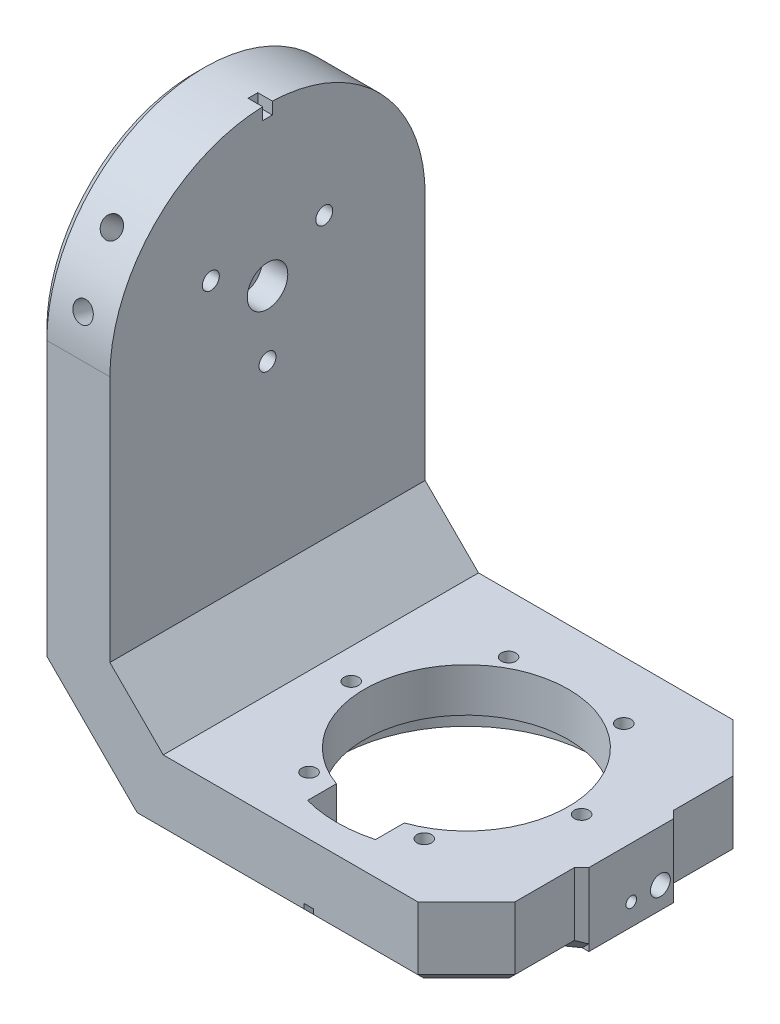
SolidWorks part; units mm, degrees
material "PETG"
ref_plane "Спереди" through (0, 0, 0) normal (0, 0, 1) x (1, 0, 0)
ref_plane "Сверху" through (0, 0, 0) normal (0, 1, 0) x (1, 0, 0)
ref_plane "Справа" through (0, 0, 0) normal (1, 0, 0) x (0, 0, -1)
sketch "Эскиз1" plane through (0, 0, 0) normal (0, 0, 1) x (1, 0, 0)
  line L0 (0, 40) -> (0, -51)
  line L1 (0, -51) -> (11, -62)
  line L2 (11, -62) -> (73.5, -62)
  line L3 (73.5, -62) -> (73.5, -77)
  line L4 (73.5, -77) -> (4.7868, -77)
  line L5 (4.7868, -77) -> (-15, -57.2132)
  line L6 (-15, -57.2132) -> (-15, 40)
  line L7 (-15, 40) -> (0, 40)
  line L8 (41, -24.4112) -> (41, -69.1198) construction
  line L9 (0, 0) -> (71, 0) construction
  dimension "D1" = 15
  dimension "D2" = 40
  dimension "D3" = 45
  dimension "D4" = 15
  dimension "D5" = 15
  dimension "D6" = 41
  dimension "D7" = 32.5
  dimension "D9" = 51
  dimension "D10" = 11
  dimension "D8" = 30
extrude "Бобышка-Вытянуть1" add sketch "Эскиз1" along normal mid plane 65
sketch "Эскиз2" plane through (-15, 0, 0) normal (-1, 0, 0) x (0, 0, 1)
  line L0 (32.5, 40) -> (32.5, -57.2132) construction
  line L1 (32.5, 40) -> (-32.5, 40) construction
  line L2 (-32.5, 40) -> (-32.5, -57.2132) construction
  line L3 (32.5, 40) -> (32.5, 0)
  line L4 (32.5, 40) -> (-32.5, 40)
  line L5 (-32.5, 40) -> (-32.5, -57.2132)
  arc A0 (32.5, 0) -> (-32.5, 0) centre (0, 0) ccw
  circle A1 centre (0, 0) radius 13.5 construction
  circle A2 centre (0, -13.5) radius 1.75
  circle A3 centre (-11.6913, 6.75) radius 1.75
  circle A4 centre (11.6913, 6.75) radius 1.75
  point P17 (0, 0)
  line M3 (-32.5, 40) -> (-32.5, -57.2132)
  line M5 (32.5, -57.2132) -> (32.5, 40)
  line M6 (32.5, 40) -> (-32.5, 40)
  dimension "D1" = 27
  dimension "D2" = 3.5
  dimension "D3" = 3
extrude "Вырез-Вытянуть1" cut sketch "Эскиз2" against normal through all contours A0 M5 M6 M3 | A2 | A4 | A3
sketch "Эскиз3" plane through (0, -77, 0) normal (0, -1, 0) x (1, 0, 0)
  line L0 (73.5, 32.5) -> (73.5, -32.5) construction
  line L1 (41, 26.675) -> (41, 32.5) construction
  line L2 (4.7868, 32.5) -> (73.5, 32.5) construction
  circle A0 centre (41, 0) radius 26.675
  dimension "D1" = 53.35
  dimension "D2" = 32.5
extrude "Вырез-Вытянуть2" cut sketch "Эскиз3" against normal blind 6
sketch "Эскиз4" plane through (0, -71, 0) normal (0, -1, 0) x (1, 0, 0)
  line L0 (73.5, 32.5) -> (73.5, -32.5) construction
  circle A0 centre (41, 0) radius 23.75 construction
  circle A1 centre (64.75, 0) radius 1.5
  circle A2 centre (52.875, -20.5681) radius 1.5
  circle A3 centre (29.125, -20.5681) radius 1.5
  circle A4 centre (17.25, 0) radius 1.5
  circle A5 centre (29.125, 20.5681) radius 1.5
  circle A6 centre (52.875, 20.5681) radius 1.5
  circle A7 centre (41, 0) radius 21
  point P17 (41, 0)
  dimension "D1" = 47.5
  dimension "D2" = 3
  dimension "D4" = 42
  dimension "D5" = 32.5
  dimension "D3" = 6
extrude "Вырез-Вытянуть3" cut sketch "Эскиз4" against normal up to next
sketch "Эскиз5" plane through (0, 0, 0) normal (1, 0, 0) x (0, 0, -1)
  circle A0 centre (0, 0) radius 4.175
  dimension "D1" = 8.35
extrude "Вырез-Вытянуть4" cut sketch "Эскиз5" against normal blind 5.2
chamfer "Фаска1" distance 10 angle 45 2 edges at (73.5, -69.5, -32.5) (73.5, -69.5, 32.5)
sketch "Эскиз6" plane through (0, -71, 0) normal (0, -1, 0) x (1, 0, 0)
  line L0 (41, 0) -> (41, 30.6158) construction
  line L1 (48, 19.799) -> (48, 28.2402)
  line L2 (34, 19.799) -> (34, 28.2402)
  line L4 (34, 0) -> (34, 30.6158) construction
  line L5 (48, 0) -> (48, 30.6158) construction
  circle A0 centre (41, 0) radius 21 construction
  arc A3 (48, 19.799) -> (34, 19.799) centre (41, 0) ccw
  circle A5 centre (41, 0) radius 26.675
  circle A6 centre (41, 0) radius 26.675
  circle M3 centre (41, 0) radius 21
  circle M15 centre (41, 0) radius 26.675
  dimension "D2" = 7
  dimension "D1" = 0
  dimension "D3" = 7
extrude "Вырез-Вытянуть5" cut sketch "Эскиз6" against normal up to next contours L2 L1 M3 M15
sketch "Эскиз7" plane through (-15, 0, 0) normal (-1, 0, 0) x (0, 0, 1)
  circle A0 centre (11.6913, 6.75) radius 3.25
  circle A1 centre (0, -13.5) radius 3.25
  circle A2 centre (-11.6913, 6.75) radius 3.25
  point P9 (0, 0)
  dimension "D1" = 6.5
  dimension "D2" = 3
extrude "Вырез-Вытянуть6" cut sketch "Эскиз7" against normal blind 3
chamfer "Фаска2" distance 2 angle 45 10 edges at (-15, -28.6066, -32.5) (-15, 32.5, 0) (-5.1066, -67.1066, -32.5) (34.1434, -77, -32.5) (68.5, -77, -27.5) (73.5, -77, 0) (68.5, -77, 27.5) (34.1434, -77, 32.5) (-5.1066, -67.1066, 32.5) (-15, -28.6066, 32.5)
ref_plane "Плоскость1" through (-6.5, 0, 0) normal (1, 0, 0) x (0, 0, -1)
sketch "Эскиз9" plane through (-6.5, 0, 0) normal (1, 0, 0) x (0, 0, -1)
  line L0 (0, 0) -> (-33.5693, 26.2272) construction
  line L1 (0, 0) -> (0, 37.5) construction
  line L2 (-19.7003, 15.3915) -> (-18.4382, 17.007)
  line L3 (-18.4382, 17.007) -> (-24.7422, 21.9323)
  line L4 (-24.7422, 21.9323) -> (-26.0044, 20.3168)
  line L5 (-26.0044, 20.3168) -> (-19.7003, 15.3915)
  circle A1 centre (0, 0) radius 37.5 construction
  dimension "D1" = 52
  dimension "D2" = 4.1
  dimension "D3" = 8
  dimension "D4" = 33
revolve "Вырез-Повернуть1" cut sketch "Эскиз9" angle 360 about L0
pattern_circular "Круговой массив1" count 2 every 24 about axis through (73.5, 0, 0) along (-1, 0, 0) of "Вырез-Повернуть1"
sketch "Эскиз10" plane through (0, 0, 0) normal (1, 0, 0) x (0, 0, -1)
  line L1 (-1, 30) -> (1, 30)
  line L2 (-1, 30) -> (-1, 33)
  line L3 (-1, 33) -> (1, 33)
  line L4 (1, 30) -> (1, 33)
  line L5 (-1, 30) -> (1, 33) construction
  line L6 (-1, 33) -> (1, 30) construction
  point P0 (0, 31.5)
  point P5 (1, 31.5)
  dimension "D1" = 33
  dimension "D2" = 2
  dimension "D3" = 3
extrude "Вырез-Вытянуть7" cut sketch "Эскиз10" against normal blind 3
sketch "Эскиз11" plane through (0, -77, 0) normal (0, -1, 0) x (1, 0, 0)
  line L0 (71.5, -21.6716) -> (71.5, 21.6716) construction
  line L1 (71.5, 8.75) -> (75, 8.75)
  line L2 (71.5, 8.75) -> (71.5, -8.75)
  line L3 (71.5, -8.75) -> (75, -8.75)
  line L4 (75, 8.75) -> (75, -8.75)
  line L5 (71.5, 8.75) -> (75, -8.75) construction
  line L6 (71.5, -8.75) -> (75, 8.75) construction
  arc A1 (34, 25.7402) -> (48, 25.7402) centre (41, 0) ccw construction
  point P0 (73.25, 0)
  dimension "D1" = 34
  dimension "D2" = 17.5
extrude "Бобышка-Вытянуть2" add sketch "Эскиз11" against normal blind 15
chamfer "Фаска3" distance 1.5 angle 45 4 edges at (72.5, -76, -8.75) (73.5, -68.5, -8.75) (72.5, -76, 8.75) (73.5, -68.5, 8.75)
sketch "Эскиз12" plane through (75, 0, 0) normal (1, 0, 0) x (0, 0, -1)
  circle A0 centre (0, -72.5) radius 1.1
  dimension "D1" = 2.2
extrude "Вырез-Вытянуть8" cut sketch "Эскиз12" against normal blind 3
sketch "Эскиз13" plane through (75, 0, 0) normal (1, 0, 0) x (0, 0, -1)
  line L0 (6, -72.5) -> (0, -72.5) construction
  circle A0 centre (6, -72.5) radius 2.05
  dimension "D1" = 6
  dimension "D2" = 4.1
extrude "Вырез-Вытянуть9" cut sketch "Эскиз13" against normal blind 6.5
sketch "Эскиз14" plane through (0, -77, 0) normal (0, -1, 0) x (1, 0, 0)
  line L0 (41, 0) -> (41, 26.675) construction
  line L1 (5.6152, 32.5) -> (63.5, 32.5) construction
  line L2 (42, 29.5) -> (40, 29.5)
  line L3 (42, 29.5) -> (42, 32.5)
  line L4 (42, 32.5) -> (40, 32.5)
  line L5 (40, 29.5) -> (40, 32.5)
  line L6 (42, 29.5) -> (40, 32.5) construction
  line L7 (42, 32.5) -> (40, 29.5) construction
  circle A0 centre (41, 0) radius 26.675 construction
  point P5 (41, 31)
  dimension "D1" = 2
  dimension "D2" = 3
extrude "Вырез-Вытянуть10" cut sketch "Эскиз14" against normal blind 3
equation "\"D5@Эскиз1\"=\"D1@Эскиз1\""
equation "\"D4@Эскиз1\"=\"D1@Эскиз1\""
